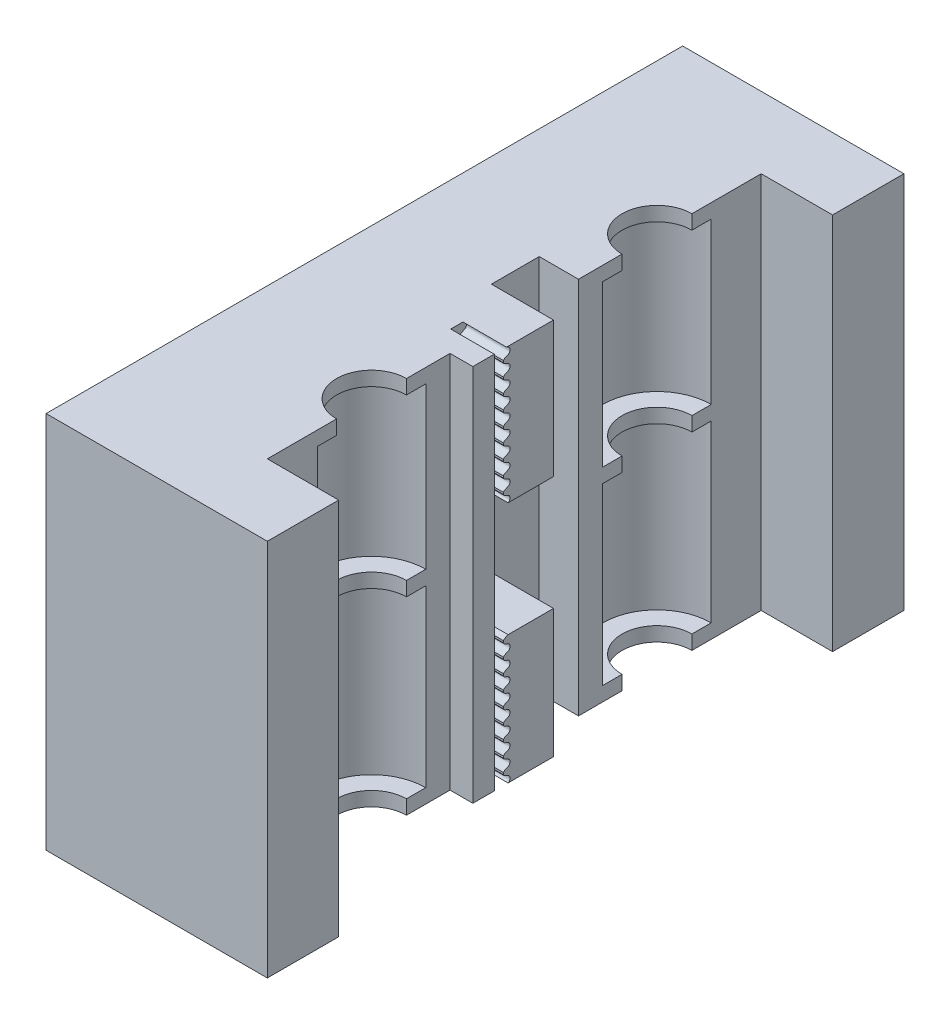
SolidWorks part; units mm, degrees
ref_plane "Front Plane" through (0, 0, 0) normal (0, 0, 1) x (1, 0, 0)
ref_plane "Top Plane" through (0, 0, 0) normal (0, 1, 0) x (1, 0, 0)
ref_plane "Right Plane" through (0, 0, 0) normal (1, 0, 0) x (0, 0, -1)
sketch "Sketch1" plane through (0, 0, 0) normal (0, 1, 0) x (1, 0, 0)
  line L0 (0, 36.6) -> (0, 43.6)
  line L1 (0, 43.6) -> (10, 43.6)
  line L2 (10, 43.6) -> (10, 53.6)
  line L3 (10, 53.6) -> (-21, 53.6)
  line L5 (-21, -35.6) -> (10, -35.6)
  line L6 (10, -35.6) -> (10, -25.6)
  line L7 (10, -25.6) -> (0, -25.6)
  line L8 (0, -25.6) -> (0, -18.6)
  line L9 (0, 21.4) -> (0, -3.4) construction
  line L10 (0, 18) -> (-5.5, 18)
  line L11 (-5.5, 18) -> (-5.5, 0)
  line L12 (-5.5, 0) -> (0, 0)
  line L24 (-21, 53.6) -> (-21, -35.6)
  line L25 (0, 0) -> (0, -3.4)
  line L26 (0, 18) -> (0, 21.4)
  arc A1 (0, 21.4) -> (0, 36.6) centre (0, 29) cw
  arc A2 (0, -18.6) -> (0, -3.4) centre (0, -11) cw
  dimension "D2" = 7.6
  dimension "D3" = 7.6
  dimension "D4" = 7
  dimension "D5" = 7
  dimension "D6" = 10
  dimension "D7" = 10
  dimension "D8" = 18
  dimension "D9" = 10
  dimension "D10" = 10
  dimension "D11" = 5.5
  dimension "D12" = 3.4
  dimension "D13" = 3.4
  dimension "D14" = 31
  dimension "D15" = 40
extrude "Boss-Extrude1" add sketch "Sketch1" along normal blind 53
sketch "Sketch2" plane through (0, 0, 0) normal (0, -1, 0) x (1, 0, 0)
  line L0 (0, 18.6) -> (0, 15.9)
  line L1 (0, 6.1) -> (0, 3.4)
  line L2 (0, -21.4) -> (0, -24.102)
  line L3 (0, -33.898) -> (0, -36.6)
  arc A0 (0, 3.4) -> (0, 18.6) centre (0, 11) cw
  arc A1 (0, 6.1) -> (0, 15.9) centre (0, 11) cw
  arc A2 (0, -36.6) -> (0, -21.4) centre (0, -29) cw
  arc A3 (0, -33.898) -> (0, -24.102) centre (0, -29) cw
  dimension "D1" = 4.9
  dimension "D2" = 4.898
extrude "Boss-Extrude2" add sketch "Sketch2" against normal blind 2
ref_plane "Plane1" through (0, 26.5, 0) normal (0, -1, 0) x (-1, 0, 0)
sketch "Sketch3" plane through (0, 26.5, 0) normal (0, -1, 0) x (-1, 0, 0)
  line L0 (0, -3.4) -> (0, -6.1)
  line L1 (0, -15.9) -> (0, -18.6)
  line L2 (0, 21.4) -> (0, 24.1)
  line L3 (0, 33.9) -> (0, 36.6)
  arc A0 (0, -18.6) -> (0, -3.4) centre (0, -11) ccw
  arc A1 (0, -15.9) -> (0, -6.1) centre (0, -11) ccw
  arc A2 (0, 36.6) -> (0, 21.4) centre (0, 29) cw
  arc A3 (0, 24.1) -> (0, 33.9) centre (0, 29) ccw
  dimension "D1" = 4.9
extrude "Boss-Extrude3" add sketch "Sketch3" against normal blind 2
ref_plane "Plane2" through (0, 51, 0) normal (0, -1, 0) x (-1, 0, 0)
sketch "Sketch4" plane through (0, 51, 0) normal (0, -1, 0) x (-1, 0, 0)
  line L0 (0, -18.6) -> (0, -15.9)
  line L1 (0, -6.1) -> (0, -3.4)
  line L2 (0, 36.6) -> (0, 33.9)
  line L3 (0, 24.1) -> (0, 21.4)
  arc A0 (0, -3.4) -> (0, -18.6) centre (0, -11) cw
  arc A1 (0, -15.9) -> (0, -6.1) centre (0, -11) ccw
  arc A2 (0, -15.9) -> (0, -6.1) centre (0, -11) ccw construction
  arc A3 (0, 21.4) -> (0, 36.6) centre (0, 29) ccw construction
  arc A5 (0, 24.1) -> (0, 33.9) centre (0, 29) ccw
  arc A6 (0, 21.4) -> (0, 36.6) centre (0, 29) ccw
  arc A7 (0, 24.1) -> (0, 33.9) centre (0, 29) ccw construction
extrude "Boss-Extrude4" add sketch "Sketch4" against normal blind 2
sketch "Sketch7" plane through (0, 53, 0) normal (0, 1, 0) x (1, 0, 0)
  line L0 (0, 0) -> (3.2, 0)
  line L1 (3.2, 0) -> (3.2, -2)
  line L2 (3.2, -2) -> (0, -2)
  line L3 (0, -6.1) -> (0, 0) construction
  line L4 (0, -2) -> (0, 0)
  dimension "D1" = 2
  dimension "D2" = 3.2
extrude "Boss-Extrude5" add sketch "Sketch7" against normal up to surface (53 mm away) up to face at (-1.4249, 0, -9)
sketch "Sketch8" plane through (0, 53, 0) normal (0, 1, 0) x (1, 0, 0)
  line L0 (0, 18) -> (0, 0) construction
  line L1 (-3.9424, 9) -> (6.0186, 9) construction
  line L2 (-5.5, 0) -> (3.2, 0)
  line L3 (3.2, 0) -> (-5.5, 0) construction
  line L4 (3.2, 0) -> (3.2, 3)
  line L5 (3.2, 3) -> (-5.5, 3)
  line L6 (-5.5, 0) -> (-5.5, 18) construction
  line L7 (-5.5, 3) -> (-5.5, 0)
  line L8 (3.2, -2) -> (3.2, 0) construction
  line L9 (-5.5, 11.3) -> (3.2, 11.3)
  line L10 (3.2, 11.3) -> (3.2, 4.3)
  line L11 (3.2, 4.3) -> (-5.5, 4.3)
  line L12 (-5.5, 4.3) -> (-5.5, 11.3)
  point P6 (0, 9)
  dimension "D1" = 3
  dimension "D2" = 7
  dimension "D3" = 1.3
extrude "Boss-Extrude6" add sketch "Sketch8" against normal up to surface (53 mm away) up to face at (-0.911, 0, -7.7778)
sketch "Sketch11" plane through (3.2, 0, 0) normal (1, 0, 0) x (0, 0, -1)
  line L0 (1264.5675, 560.6102) -> (1262.5675, 560.6102) construction
  line L1 (4.3, 0) -> (4.3, 53) construction
  line L2 (4.2853, 45.4328) -> (4.2853, 47.4569)
  spline S0 degree 3 poles (4.2853, 47.4569) (4.284, 47.4147) (4.2867, 47.3463) (4.3158, 47.2523) (4.3712, 47.1708) (4.4771, 47.1012) (4.6041, 47.0544) (4.7214, 46.9971) (4.8254, 46.9474) (4.9241, 46.9047) (5.0186, 46.8525) (5.1086, 46.7783) (5.1561, 46.6816) (5.1905, 46.5926) (5.1913, 46.5195) (5.1931, 46.4561) (5.1891, 46.3829) (5.1871, 46.2871) (5.1399, 46.1709) (5.0494, 46.057) (4.9087, 45.9856) (4.7554, 45.916) (4.621, 45.8529) (4.5075, 45.8004) (4.4122, 45.7562) (4.3028, 45.6419) (4.2855, 45.5136) (4.2853, 45.4328) knots 0 0 0 0 0.042789 0.068472 0.09859 0.140403 0.193951 0.235463 0.272242 0.310543 0.344117 0.381404 0.42616 0.451184 0.477135 0.499165 0.515432 0.551275 0.595353 0.639476 0.695379 0.752126 0.810504 0.845135 0.878871 0.916023 1 1 1 1
  line M5 (4.3, 53) -> (4.3, 0)
  dimension "D1" = 2
extrude "Cut-Extrude4" cut sketch "Sketch11" against normal up to surface (8.7 mm away) contours S0 M5 region at (3.2, 46.4474, -4.673) up to face at (-5.5, 26.5, -3.65)
pattern_linear "LPattern1" count 24 spacing 2 along (0, -1, 0) count 4 spacing 2 along (0, 1, 0) of "Cut-Extrude4"
sketch "Sketch12" plane through (3.2, 0, 0) normal (1, 0, 0) x (0, 0, -1)
  line L0 (11.3, 0) -> (11.3, 53) construction
  line L1 (11.3, 34) -> (4.3, 34)
  line L2 (11.3, 34) -> (11.3, 18)
  line L3 (11.3, 18) -> (4.3, 18)
  line L4 (4.3, 34) -> (4.3, 18)
  dimension "D1" = 18
  dimension "D2" = 19
extrude "Cut-Extrude5" cut sketch "Sketch12" against normal up to surface (8.7 mm away) up to face at (-5.5, 26.5, -14.65)
sketch "Sketch13" plane through (0, 53, 0) normal (0, 1, 0) x (1, 0, 0)
  line L0 (-5.5, 3) -> (-2.9059, 3)
  line L1 (3.2, 3) -> (-5.5, 3) construction
  line L6 (-2.9059, 3) -> (-2.9059, 7.169)
  line L7 (-2.9059, 7.169) -> (-5.5, 7.169)
  line L8 (-5.5, 18) -> (-5.5, 0) construction
  line L9 (-5.5, 7.169) -> (-5.5, 3)
extrude "Boss-Extrude16" add sketch "Sketch13" against normal up to surface (53 mm away) up to face at (-0.9545, 0, -8.1123)
sketch "Sketch14" plane through (0, 53, 0) normal (0, 1, 0) x (1, 0, 0)
  line L0 (0, 0) -> (0, -2)
  line L1 (0, -2) -> (3.2, -2)
  line L2 (3.2, -2) -> (3.2, 0)
  line L3 (3.2, -2) -> (3.2, 3) construction
  line L4 (3.2, 0) -> (0, 0)
extrude "Cut-Extrude6" cut sketch "Sketch14" against normal up to surface (53 mm away) up to face at (-0.7186, 0, -8.1123)
